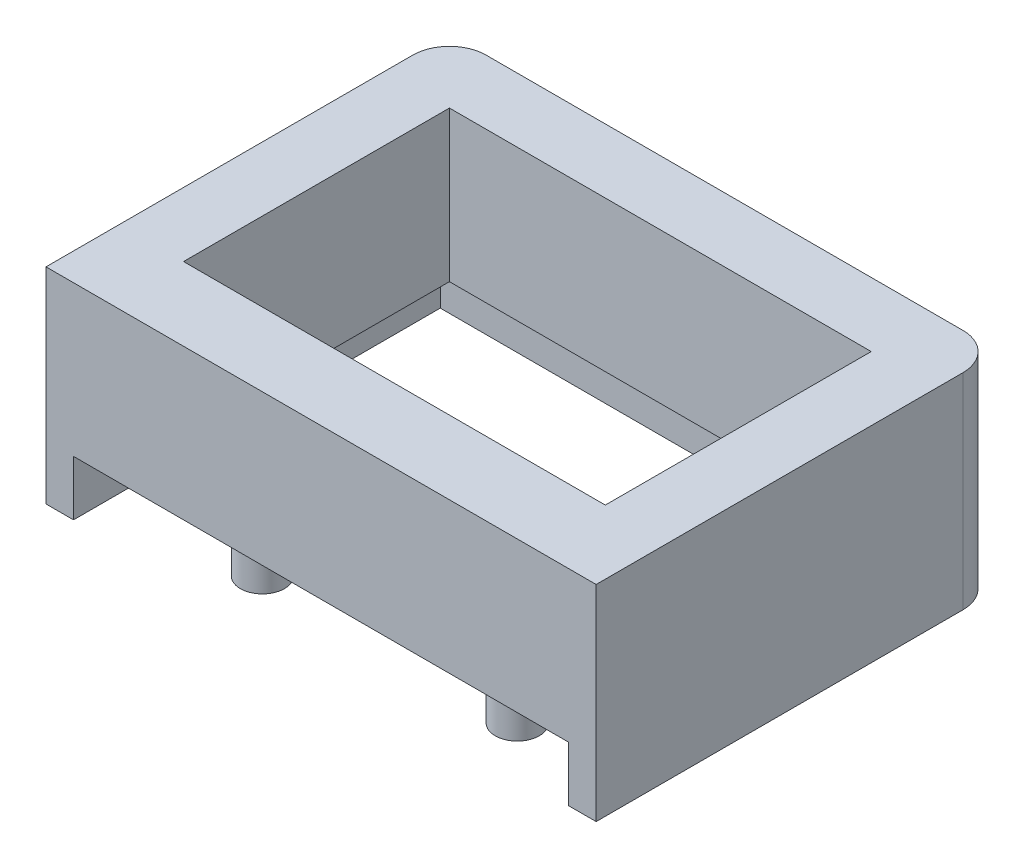
SolidWorks part; units mm, degrees
ref_plane "Plano frontal" through (0, 0, 0) normal (0, 0, 1) x (1, 0, 0)
ref_plane "Plano superior" through (0, 0, 0) normal (0, 1, 0) x (1, 0, 0)
ref_plane "Plano direito" through (0, 0, 0) normal (1, 0, 0) x (0, 0, -1)
sketch "Esboço1" plane through (0, 0, 0) normal (0, 1, 0) x (1, 0, 0)
  line L0 (-13, -9) -> (-13, -7.5)
  line L1 (-13, -10) -> (13, -10)
  line L2 (-13, -10) -> (-13, 10)
  line L3 (-13, 10) -> (13, 10)
  line L4 (13, -10) -> (13, 10)
  line L5 (-13, -10) -> (13, 10) construction
  line L6 (-13, 10) -> (13, -10) construction
  line L7 (-13, -10) -> (13, -10)
  line L8 (-13, -10) -> (-13, -9)
  line L9 (-13, -9) -> (13, -9)
  line L10 (13, -10) -> (13, -9)
  line L11 (-13, -7.5) -> (13, -7.5)
  line L12 (-13, -7.5) -> (-5.7, -7.5)
  line L13 (-4.5, -7.5) -> (8.2, -7.5)
  line L14 (-5.7, -7.5) -> (-6.9, -7.5)
  line L15 (-13, 10) -> (-11.5, 10)
  line L16 (-13, 10) -> (-13, -10)
  line L17 (-13, -10) -> (-11.5, -10)
  line L18 (-11.5, 10) -> (-11.5, -10)
  line L19 (8.2, -7.5) -> (9.4, -7.5)
  line L20 (-13, 10) -> (-13, -10)
  line L21 (-13, -10) -> (-15, -10)
  line L22 (-15, 10) -> (-15, -10)
  line L23 (-13, 10) -> (13, 10)
  line L25 (-13, 12) -> (13, 12)
  line L27 (13, 12) -> (15, 12)
  line L28 (13, 10) -> (13, -10)
  line L29 (13, -10) -> (15, -10)
  line L30 (15, 12) -> (15, -10)
  line L32 (-15, 10) -> (-15, 12)
  line L33 (-15, 12) -> (-13, 12)
  line L35 (13, 12) -> (15, 12)
  line L38 (15, 12) -> (15, 10)
  circle A0 centre (-5.7, -7.5) radius 1.2
  circle A1 centre (8.2, -7.5) radius 1.2
  point P0 (0, 0)
  dimension "D6" = 2.4
  dimension "D8" = 2.4
  dimension "D3" = 1
  dimension "D4" = 1.5
  dimension "D5" = 23.2
  dimension "D7" = 9.3
  dimension "D9" = 1.5
  dimension "D10" = 2
  dimension "D11" = 2
  dimension "D12" = 24.5
  dimension "D13" = 2
  dimension "D14" = 30
  dimension "D15" = 26
  dimension "D16" = 22
  dimension "D17" = 20
extrude "Ressalto-extrusão1" add sketch "Esboço1" along normal blind 4 contours L11 A0 | A0 L11 | A1 L11 L13 | L11 A1 L13 region at (-5.7, 0, 6.9907) region at (-5.7, 0, 8.0093) region at (8.2, 0, 8.0093) region at (8.2, 0, 6.9907)
extrude "Ressalto-extrusão2" add sketch "Esboço1<3>" along normal blind 4 separate body contours L33 L32 L22 L21 L2 L0 L3 L4 L29 L30 L27 L25 region at (-13.372, 0, 9.5)
sketch "Esboço1<3>" plane through (0, 0, 0) normal (0, 1, 0) x (1, 0, 0) same geometry as "Esboço1"
sketch "Esboço2" plane through (0, 4, 0) normal (0, 1, 0) x (1, 0, 0)
  line L0 (15, 12) -> (15, -10) construction
  line L1 (-15, -10) -> (15, -10)
  line L2 (-15, -10) -> (-15, -6)
  line L3 (-15, -6) -> (15, -6)
  line L4 (15, -10) -> (15, -6)
  dimension "D1" = 4
extrude "Ressalto-extrusão3" add sketch "Esboço2" along normal blind 5
sketch "Esboço3" plane through (0, 4, 0) normal (0, 1, 0) x (1, 0, 0)
  line L3 (-11.5, 8.5) -> (11.5, 8.5)
  line L5 (13, -6) -> (-13, -6) construction
  line L8 (-13, -6) -> (-11.5, -6)
  line L9 (-11.5, 8.5) -> (-11.5, -6)
  line L10 (13, -6) -> (-13, -6) construction
  line L11 (-15, 12) -> (15, 12)
  line L13 (13, -6) -> (11.5, -6)
  line L14 (11.5, 8.5) -> (11.5, -6)
  line L15 (-15, 12) -> (-15, -6)
  line L16 (-15, -6) -> (15, -6)
  line L17 (15, 12) -> (15, -6)
  line M7 (13, -6) -> (15, -6)
  line M8 (15, -6) -> (15, 12)
  line M9 (15, 12) -> (-15, 12)
  line M10 (-15, 12) -> (-15, -6)
  line M11 (-15, -6) -> (-13, -6)
  line M12 (-13, -6) -> (-13, 10)
  line M13 (-13, 10) -> (13, 10)
  line M14 (13, 10) -> (13, -6)
extrude "Ressalto-extrusão4" add sketch "Esboço3" along normal blind 5 contours L3 L14 L13 L8 L9 M14 M13 M12 | M14 M7 M8 M9 M10 M11 M12 M13 region at (-11.8053, 4, -1.25) region at (-14, 4, 5.6501)
sketch "Esboço4" plane through (0, 0, 0) normal (0, -1, 0) x (1, 0, 0)
  line L0 (-13, 10) -> (-15, 10) construction
  line L1 (-13, -10) -> (-13.5, -10)
  line L2 (-13, -10) -> (-13, 10)
  line L3 (-13, 10) -> (-13.5, 10)
  line L4 (-13.5, -10) -> (-13.5, 10)
  line L5 (13, 10) -> (15, 10) construction
  line L6 (13, -10) -> (13.5, -10)
  line L7 (13, -10) -> (13, 10)
  line L8 (13, 10) -> (13.5, 10)
  line L9 (13.5, -10) -> (13.5, 10)
  line L10 (15, 10) -> (15, 3.2151)
  line L11 (15, -12) -> (15, 10) construction
  line L12 (-15, 10) -> (-15, 4.5279)
  line L13 (-15, 10) -> (-15, -12) construction
  dimension "D1" = 0.5
  dimension "D2" = 0.5
sketch "Esboço5" plane through (-15, 0, 0) normal (-1, 0, 0) x (0, 0, 1)
  line L0 (-12, 9) -> (-12, 0) construction
  line L1 (10, 0) -> (-12, 0)
  line L2 (10, 0) -> (10, 1)
  line L3 (10, 1) -> (-12, 1)
  line L4 (-12, 0) -> (-12, 1)
  dimension "D1" = 1
extrude "Corte-extrusão2" cut sketch "Esboço5" against normal blind 35
sketch "Esboço8" plane through (0, 1, 0) normal (0, -1, 0) x (1, 0, 0)
  line L0 (15, 10) -> (13, 10) construction
  line L1 (-13, -12) -> (13, -12)
  line L2 (-15, -10) -> (-15, 10)
  line L3 (-15, 10) -> (15, 10)
  line L4 (15, -10) -> (15, 10)
  line L5 (15, -10) -> (15, -12)
  line L6 (15, -12) -> (-15, -12)
  line L7 (-15, -12) -> (-15, -10)
  arc A0 (13, -12) -> (15, -10) centre (13, -10) ccw
  arc A1 (-13, -12) -> (-15, -10) centre (-13, -10) cw
  point P11 (-15, -12)
  line M6 (-15, 10) -> (-15, -12)
  line M7 (-15, -12) -> (15, -12)
  line M8 (15, -12) -> (15, 10)
  dimension "D1" = 2
extrude "Corte-extrusão3" cut sketch "Esboço8" against normal blind 10 contours A1 M7 M6 | A0 M7 M8 region at (-14.5533, 1, -11.5533) region at (14.5533, 1, -11.5533)
sketch "Esboço9" plane through (0, 9, 0) normal (0, 1, 0) x (1, 0, 0)
  line L0 (11.5, 8.5) -> (11.5, -6) construction
  line L1 (11.5, -6) -> (-11.5, -6) construction
  line L2 (-11.5, 8.5) -> (11.5, 8.5) construction
  line L3 (-11.5, 8.5) -> (-11.5, -6) construction
  line L4 (13, 12) -> (-13, 12)
  line L5 (-15, 10) -> (-15, -10)
  line L6 (-15, -10) -> (15, -10)
  line L7 (15, -10) -> (15, 10)
  line L8 (13, 12) -> (-13, 12)
  line L9 (-15, 10) -> (-15, -10)
  line L10 (-15, -10) -> (15, -10)
  line L11 (15, -10) -> (15, 10)
  line L12 (11.5, 8.5) -> (11.5, -6)
  line L13 (11.5, -6) -> (-11.5, -6)
  line L14 (-11.5, 8.5) -> (11.5, 8.5)
  line L15 (-11.5, 8.5) -> (-11.5, -6)
  arc A2 (15, 10) -> (13, 12) centre (13, 10) ccw
  arc A3 (-13, 12) -> (-15, 10) centre (-13, 10) ccw
  arc A4 (15, 10) -> (13, 12) centre (13, 10) ccw
  arc A5 (-13, 12) -> (-15, 10) centre (-13, 10) ccw
  dimension "D1" = 0
extrude "Ressalto-extrusão5" add sketch "Esboço9" along normal blind 3.2
extrude "Corte-extrusão4" cut sketch "Esboço4" against normal blind 4 contours L9 L8 L7 L6 | L2 L3 L4 L1
ref_plane "Plano2" through (0, 3, 0) normal (0, -1, 0) x (-1, 0, 0)
sketch "Esboço11" plane through (0, 4, 0) normal (0, -1, 0) x (1, 0, 0)
  circle A0 centre (8.2, 7.5) radius 1.5
  circle A1 centre (-5.7, 7.5) radius 1.5
  dimension "D1" = 3
  dimension "D2" = 3
ref_plane "Plano3" through (0, 3, 0) normal (0, -1, 0) x (-1, 0, 0)
sketch "Esboço12" plane through (0, 3, 0) normal (0, -1, 0) x (-1, 0, 0)
  circle A0 centre (5.7, -7.5) radius 1.3
  circle A1 centre (-8.2, -7.5) radius 1.3
  dimension "D1" = 2.6
  dimension "D2" = 2.6
loft "Loft4" add section "Esboço11" section "Esboço12" connector at (-7.1679, 4, 7.1912) connector at (-6.9531, 3, 7.1538)
loft "Loft5" add section "Esboço11<4>" section "Esboço12<4>" connector at (6.7827, 4, 7.0088) connector at (6.9575, 3, 7.1177)
sketch "Esboço11<4>" plane through (0, 4, 0) normal (0, -1, 0) x (1, 0, 0) same geometry as "Esboço11"
sketch "Esboço12<4>" plane through (0, 3, 0) normal (0, -1, 0) x (-1, 0, 0) same geometry as "Esboço12"
